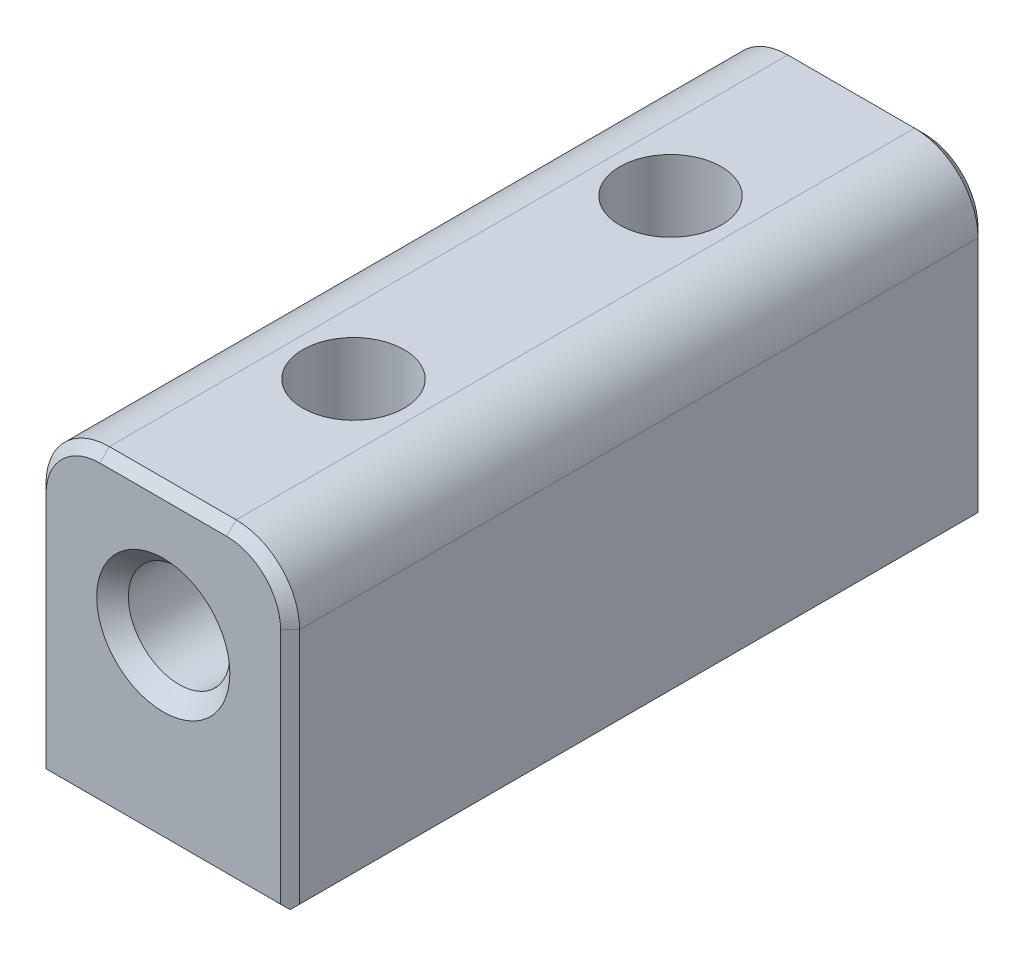
SolidWorks part; units mm, degrees
ref_plane "Front Plane" through (0, 0, 0) normal (0, 0, 1) x (1, 0, 0)
ref_plane "Top Plane" through (0, 0, 0) normal (0, 1, 0) x (1, 0, 0)
ref_plane "Right Plane" through (0, 0, 0) normal (1, 0, 0) x (0, 0, -1)
sketch "Sketch1" plane through (0, 0, 0) normal (0, 1, 0) x (1, 0, 0)
  line L0 (0, -6.35) -> (0, 6.35) construction
  line L1 (5.08, -13.97) -> (-5.08, -13.97)
  line L2 (5.08, -13.97) -> (5.08, 13.97)
  line L3 (5.08, 13.97) -> (-5.08, 13.97)
  line L4 (-5.08, -13.97) -> (-5.08, 13.97)
  line L5 (5.08, -13.97) -> (-5.08, 13.97) construction
  line L6 (5.08, 13.97) -> (-5.08, -13.97) construction
  circle A0 centre (0, 6.35) radius 2.032
  circle A1 centre (0, -6.35) radius 2.032
  point P0 (0, 0)
  point P9 (0, 0)
  point P11 (0, 0)
  dimension "D4" = 4.064
  dimension "D1" = 27.94
  dimension "D2" = 10.16
  dimension "D3" = 12.7
extrude "Boss-Extrude1" add sketch "Sketch1" along normal blind 12.7
sketch "Sketch2" plane through (0, 0, 13.97) normal (0, 0, 1) x (1, 0, 0)
  line L0 (-5.08, 0) -> (5.08, 0) construction
  line L1 (-5.08, 12.7) -> (-5.08, 0) construction
  circle A0 centre (0, 7.62) radius 2.032
  dimension "D1" = 4.064
  dimension "D2" = 7.62
  dimension "D3" = 5.08
extrude "Cut-Extrude1" cut sketch "Sketch2" against normal blind 3.81
sketch "Sketch4" plane through (0, 0, -13.97) normal (0, 0, -1) x (-1, 0, 0)
  line L0 (-5.08, 0) -> (5.08, 0) construction
  line L1 (-5.08, 12.7) -> (-5.08, 0) construction
  circle A0 centre (0, 7.62) radius 2.032
  dimension "D1" = 4.064
  dimension "D2" = 7.62
  dimension "D3" = 5.08
extrude "Cut-Extrude2" cut sketch "Sketch4" against normal blind 3.81
fillet "Fillet1" radius 2.54 2 edges at (5.08, 12.7, 0) (-5.08, 12.7, 0)
chamfer "Chamfer1" distance 0.635 angle 45 8 edges at (0, 0, 8.382) (0, 0, -4.318) (0, 0, 13.97) (5.08, 0, 0) (0, 0, -13.97) (-5.08, 0, 0) (-2.032, 7.62, -13.97) (2.032, 7.62, 13.97)
chamfer "Chamfer2" distance 0.381 angle 45 10 edges at (-5.08, 5.3975, -13.97) (-4.3361, 11.9561, -13.97) (0, 12.7, -13.97) (4.3361, 11.9561, -13.97) (5.08, 5.3975, -13.97) (-5.08, 5.3975, 13.97) (-4.3361, 11.9561, 13.97) (0, 12.7, 13.97) (4.3361, 11.9561, 13.97) (5.08, 5.3975, 13.97)
